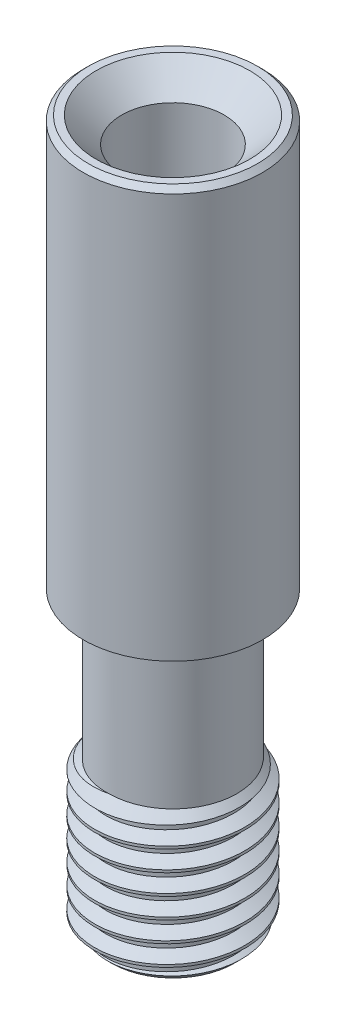
SolidWorks part; units mm, degrees
ref_plane "前视基准面" through (0, 0, 0) normal (0, 0, 1) x (1, 0, 0)
ref_plane "上视基准面" through (0, 0, 0) normal (0, 1, 0) x (1, 0, 0)
ref_plane "右视基准面" through (0, 0, 0) normal (1, 0, 0) x (0, 0, -1)
sketch "草图2" plane through (0, 0, 0) normal (0, 0, 1) x (1, 0, 0)
  line L0 (0, 0) -> (0, 11.3747) construction
  line L1 (-2, -13.0262) -> (-2, 14.4738)
  line L2 (-2, 14.4738) -> (-3.5, 14.4738)
  line L3 (-3.5, 14.4738) -> (-3.5, -1.5262)
  line L4 (-3.5, -1.5262) -> (-2.5, -2.1036)
  line L5 (-2.5, -2.1036) -> (-2.5, -13.0262)
  line L6 (-2.5, -13.0262) -> (-2, -13.0262)
  dimension "D1" = 3.5
  dimension "D2" = 27.5
  dimension "D3" = 16
  dimension "D4" = 60
  dimension "D5" = 4
  dimension "D6" = 2.5
revolve "旋转1" add sketch "草图2" angle 360 about L0
thread "螺纹线1" pitch 0.8 method extrude trim with start face yes profile "螺纹线轮廓1" start angle 0, offset 1, length 6.85, pitch 0.8, diameter 5
ref_plane "基准面1" through (2.5, -14.0262, 0) normal (0, 0, 1) x (1, 0, 0)
sketch "螺纹线轮廓1" plane through (2.5, -14.0262, 0) normal (0, 0, 1) x (1, 0, 0)
  line L0 (0, 0) -> (0, 0.8) construction
  line L1 (0, 0) -> (0.433, 0.25)
  line L2 (0.433, 0.25) -> (0.433, 0.35)
  line L3 (0.433, 0.35) -> (0, 0.6)
  line L4 (0.433, 0.3) -> (0, 0.3) construction
  line L11 (0, 0) -> (0, 0.6)
  point P2 (0, 0)
  dimension "Pitch" = 0.8
  dimension "Profile_Angle" = 60
  dimension "Profile_Land" = 0.1
  dimension "Profile_Height" = 0.433
sketch "草图6" plane through (0, 0, 0) normal (0, 0, 1) x (1, 0, 0)
  line L1 (-2.5, -2.1036) -> (-2.5, -6.6262) construction
  line L2 (-2.5, -7.2262) -> (-3.4205, -8.1468)
  line L3 (-3.4205, -8.1468) -> (-3.4205, -11.9886)
  line L4 (-3.4205, -11.9886) -> (-1.9477, -13.4615)
  line L5 (-1.9477, -13.4615) -> (-1.9477, -15.0893)
  line L6 (-1.9477, -15.0893) -> (-6.0039, -15.0893)
  line L7 (-6.0039, -15.0893) -> (-6.0039, -5.0386)
  line L8 (-6.0039, -5.0386) -> (-2.5, -5.0386)
  line L9 (2.933, -7.6592) -> (-4.1087, -7.6592) construction
  line L10 (-2.5, -5.0386) -> (-2.5, -7.2262)
  line L11 (3.142, -12.4761) -> (-3.9432, -12.4761) construction
  line L13 (-2.933, -12.5648) -> (-2.933, -12.4761) construction
  line L14 (-2.933, -12.4762) -> (-2.933, -12.5762) construction
  line L15 (-2.933, -12.4761) -> (-2.933, -7.6592) construction
  line L17 (0, 0) -> (0, -17.369) construction
  line L18 (-2.5, -7.2262) -> (-2.5, -7.4262) construction
  spline S0 degree 2 poles (0, -13.0262) (-1.0355, -12.9762) (-1.7678, -12.9262) (-2.5, -12.8762) (-2.5, -12.8262) (-2.5, -12.7762) (-1.7678, -12.7262) (-1.0355, -12.6762) (0, -12.6262) (1.0355, -12.5762) (1.7678, -12.5262) (2.5, -12.4762) (2.5, -12.4262) (2.5, -12.3762) (1.7678, -12.3262) (1.0355, -12.2762) (0, -12.2262) (-1.0355, -12.1762) (-1.7678, -12.1262) (-2.5, -12.0762) (-2.5, -12.0262) (-2.5, -11.9762) (-1.7678, -11.9262) (-1.0355, -11.8762) (0, -11.8262) (1.0355, -11.7762) (1.7678, -11.7262) (2.5, -11.6762) (2.5, -11.6262) (2.5, -11.5762) (1.7678, -11.5262) (1.0355, -11.4762) (0, -11.4262) (-1.0355, -11.3762) (-1.7678, -11.3262) (-2.5, -11.2762) (-2.5, -11.2262) (-2.5, -11.1762) (-1.7678, -11.1262) (-1.0355, -11.0762) (0, -11.0262) (1.0355, -10.9762) (1.7678, -10.9262) (2.5, -10.8762) (2.5, -10.8262) (2.5, -10.7762) (1.7678, -10.7262) (1.0355, -10.6762) (0, -10.6262) (-1.0355, -10.5762) (-1.7678, -10.5262) (-2.5, -10.4762) (-2.5, -10.4262) (-2.5, -10.3762) (-1.7678, -10.3262) (-1.0355, -10.2762) (0, -10.2262) (1.0355, -10.1762) (1.7678, -10.1262) (2.5, -10.0762) (2.5, -10.0262) (2.5, -9.9762) (1.7678, -9.9262) (1.0355, -9.8762) (0, -9.8262) (-1.0355, -9.7762) (-1.7678, -9.7262) (-2.5, -9.6762) (-2.5, -9.6262) (-2.5, -9.5762) (-1.7678, -9.5262) (-1.0355, -9.4762) (0, -9.4262) (1.0355, -9.3762) (1.7678, -9.3262) (2.5, -9.2762) (2.5, -9.2262) (2.5, -9.1762) (1.7678, -9.1262) (1.0355, -9.0762) (0, -9.0262) (-1.0355, -8.9762) (-1.7678, -8.9262) (-2.5, -8.8762) (-2.5, -8.8262) (-2.5, -8.7762) (-1.7678, -8.7262) (-1.0355, -8.6762) (0, -8.6262) (1.0355, -8.5762) (1.7678, -8.5262) (2.5, -8.4762) (2.5, -8.4262) (2.5, -8.3762) (1.7678, -8.3262) (1.0355, -8.2762) (0, -8.2262) (-1.0355, -8.1762) (-1.7678, -8.1262) (-2.5, -8.0762) (-2.5, -8.0262) (-2.5, -7.9762) (-1.7678, -7.9262) (-1.0355, -7.8762) (0, -7.8262) (1.0355, -7.7762) (1.7678, -7.7262) (2.5, -7.6762) (2.5, -7.6262) (2.5, -7.5762) (1.7678, -7.5262) (1.0355, -7.4762) (0, -7.4262) (-1.0355, -7.3762) (-1.7678, -7.3262) (-2.5, -7.2762) (-2.5, -7.2262) (-2.5, -7.2022) (-2.3097, -7.1762) knots 0.138889 0.138889 0.138889 0.152778 0.152778 0.166667 0.166667 0.180556 0.180556 0.194444 0.194444 0.208333 0.208333 0.222222 0.222222 0.236111 0.236111 0.25 0.25 0.263889 0.263889 0.277778 0.277778 0.291667 0.291667 0.305556 0.305556 0.319444 0.319444 0.333333 0.333333 0.347222 0.347222 0.361111 0.361111 0.375 0.375 0.388889 0.388889 0.402778 0.402778 0.416667 0.416667 0.430556 0.430556 0.444444 0.444444 0.458333 0.458333 0.472222 0.472222 0.486111 0.486111 0.5 0.5 0.513889 0.513889 0.527778 0.527778 0.541667 0.541667 0.555556 0.555556 0.569444 0.569444 0.583333 0.583333 0.597222 0.597222 0.611111 0.611111 0.625 0.625 0.638889 0.638889 0.652778 0.652778 0.666667 0.666667 0.680556 0.680556 0.694444 0.694444 0.708333 0.708333 0.722222 0.722222 0.736111 0.736111 0.75 0.75 0.763889 0.763889 0.777778 0.777778 0.791667 0.791667 0.805556 0.805556 0.819444 0.819444 0.833333 0.833333 0.847222 0.847222 0.861111 0.861111 0.875 0.875 0.888889 0.888889 0.902778 0.902778 0.916667 0.916667 0.930556 0.930556 0.944444 0.944444 0.951389 0.951389 0.951389 weights 1 0.92388 1 0.92388 1 0.92388 1 0.92388 1 0.92388 1 0.92388 1 0.92388 1 0.92388 1 0.92388 1 0.92388 1 0.92388 1 0.92388 1 0.92388 1 0.92388 1 0.92388 1 0.92388 1 0.92388 1 0.92388 1 0.92388 1 0.92388 1 0.92388 1 0.92388 1 0.92388 1 0.92388 1 0.92388 1 0.92388 1 0.92388 1 0.92388 1 0.92388 1 0.92388 1 0.92388 1 0.92388 1 0.92388 1 0.92388 1 0.92388 1 0.92388 1 0.92388 1 0.92388 1 0.92388 1 0.92388 1 0.92388 1 0.92388 1 0.92388 1 0.92388 1 0.92388 1 0.92388 1 0.92388 1 0.92388 1 0.92388 1 0.92388 1 0.92388 1 0.92388 1 0.92388 1 0.92388 1 0.92388 1 0.92388 1 0.92388 1 0.92388 1 0.96194 0.96194 construction
  dimension "D1" = 225
  dimension "D2" = 135
revolve "切除-旋转1" cut sketch "草图6" angle 360 about L17
chamfer "倒角1" distance 0.2 angle 45 2 edges at (0, -13.0262, -2) (0, 14.4738, -3.5)
chamfer "倒角2" distance 1 angle 45 1 edges at (0, 14.4738, -2)
